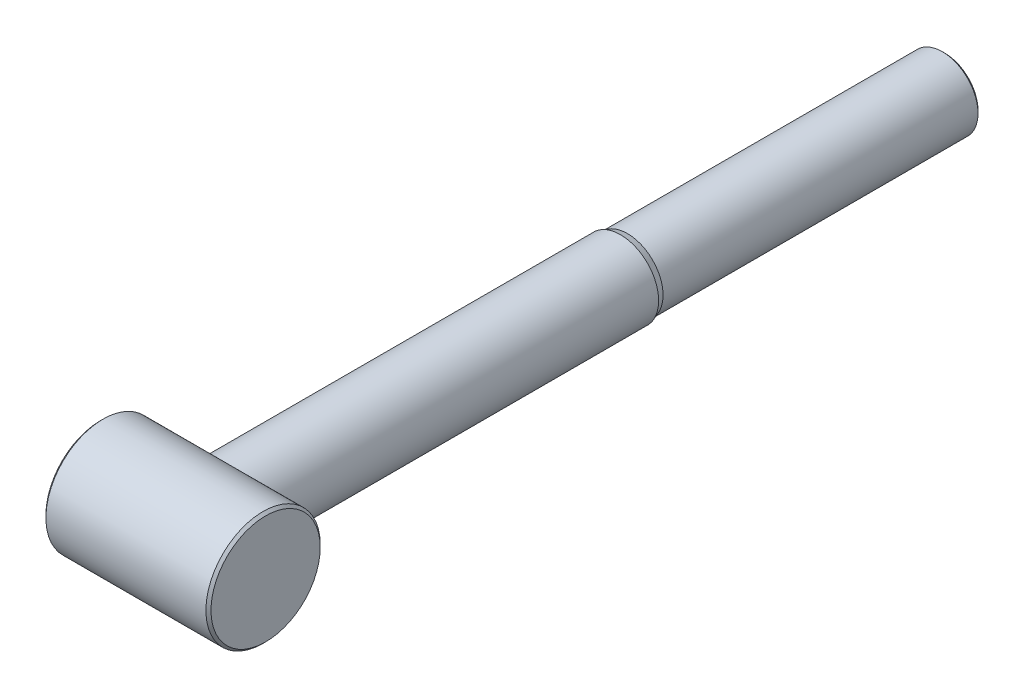
SolidWorks part; units mm, degrees
material "Č0361"
ref_plane "Front Plane" through (0, 0, 0) normal (0, 0, 1) x (1, 0, 0)
ref_plane "Top Plane" through (0, 0, 0) normal (0, 1, 0) x (1, 0, 0)
ref_plane "Right Plane" through (0, 0, 0) normal (1, 0, 0) x (0, 0, -1)
sketch "Sketch1" plane through (0, 0, 0) normal (1, 0, 0) x (0, 0, -1)
  circle A0 centre (0, 0) radius 4.5
  dimension "D1" = 9
extrude "Boss-Extrude1" add sketch "Sketch1" along normal mid plane 13
sketch "Sketch2" plane through (0, 0, 0) normal (0, 0, 1) x (1, 0, 0)
  circle A0 centre (0, 0) radius 3
  dimension "D1" = 6
extrude "Boss-Extrude2" add sketch "Sketch2" against normal blind 60
sketch "Sketch3" plane through (0, 0, -60) normal (0, 0, -1) x (-1, 0, 0)
  circle A0 centre (0, 0) radius 3 construction
  circle A1 centre (0, 0) radius 3
extrude "Cut-Extrude-Thin1" cut sketch "Sketch3" against normal blind 25 thin thin type one direction reverse wall 0.2
chamfer "Chamfer1" distance 0.2 angle 70 1 edges at (-3, 0, -35) first distance on face at (-2.8, 0, -35)
chamfer "Chamfer2" distance 0.2 angle 45 2 edges at (-6.5, 0, -4.5) (6.5, 0, -4.5)
chamfer "Chamfer3" distance 0.2 angle 45 1 edges at (-2.8, 0, -60)
